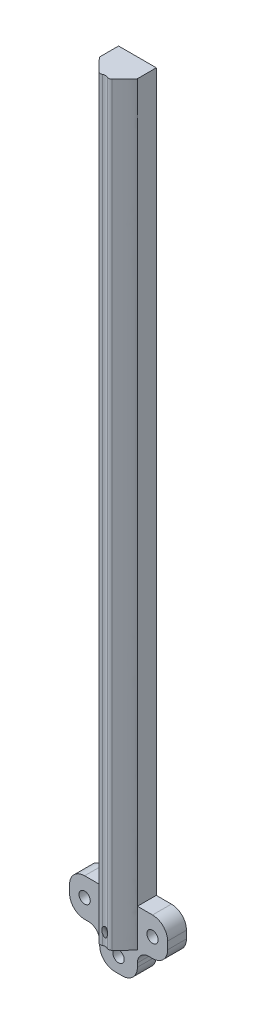
SolidWorks part; units mm, degrees
ref_plane "Front Plane" through (0, 0, 0) normal (0, 0, 1) x (1, 0, 0)
ref_plane "Top Plane" through (0, 0, 0) normal (0, 1, 0) x (1, 0, 0)
ref_plane "Right Plane" through (0, 0, 0) normal (1, 0, 0) x (0, 0, -1)
sketch "Sketch1" plane through (0, 0, 0) normal (0, 1, 0) x (1, 0, 0)
  line L1 (0, 0) -> (10, 0)
  line L2 (0, 0) -> (0, -10)
  line L3 (0, -10) -> (10, -10)
  line L4 (10, 0) -> (10, -10)
  dimension "D1" = 10
  dimension "D2" = 10
extrude "Boss-Extrude1" add sketch "Sketch1" along normal blind 200
fillet "Fillet1" radius 5 2 edges at (0, 100, 10) (10, 100, 10) conic rho 0.05
sketch "Sketch2" plane through (0, 0, 0) normal (0, -1, 0) x (-1, 0, 0)
  circle A0 centre (-5, -10) radius 1.5
  dimension "D1" = 3
extrude "Cut-Extrude1" cut sketch "Sketch2" against normal through all
fillet "Fillet2" radius 1 2 edges
sketch "Sketch4" plane through (0, 0, 0) normal (0, 0, -1) x (-1, 0, 0)
  line L1 (0, 0) -> (8, 0)
  line L2 (0, 0) -> (0, 10)
  line L3 (0, 10) -> (8, 10)
  line L4 (8, 0) -> (8, 10)
  line L5 (-10, 0) -> (-18, 0)
  line L6 (-10, 0) -> (-10, 10)
  line L7 (-10, 10) -> (-18, 10)
  line L8 (-18, 0) -> (-18, 10)
  dimension "D1" = 8
  dimension "D2" = 8
  dimension "D3" = 10
  dimension "D4" = 10
extrude "Boss-Extrude2" add sketch "Sketch4" against normal blind 5
sketch "Sketch5" plane through (0, 0, 0) normal (0, -1, 0) x (-1, 0, 0)
  line L0 (-18, 0) -> (8, 0) construction
  line L1 (0, 0) -> (-10, 0)
  line L2 (0, 0) -> (0, -5)
  line L3 (0, -5) -> (-10, -5)
  line L4 (-10, 0) -> (-10, -5)
  dimension "D1" = 5
  dimension "D2" = 0
  dimension "D3" = 0
extrude "Boss-Extrude3" add sketch "Sketch5" along normal blind 8
fillet "Fillet3" radius 4 6 edges at (18, 10, 2.5) (18, 0, 2.5) (10, -8, 2.5) (0, -8, 2.5) (-8, 10, 2.5) (-8, 0, 2.5)
fillet "Fillet4" radius 3 2 edges
sketch "Sketch6" plane through (0, 0, 5) normal (0, 0, 1) x (1, 0, 0)
  line L0 (-4, 10) -> (0, 10) construction
  line L1 (-8, 4) -> (-8, 6) construction
  line L2 (10, 10) -> (14, 10) construction
  line L3 (18, 6) -> (18, 4) construction
  line L4 (6, -8) -> (4, -8) construction
  line L5 (0, -4) -> (0, -3) construction
  circle A0 centre (-4, 5) radius 1.5
  circle A1 centre (14, 5) radius 1.5
  circle A2 centre (5, -4) radius 1.5
  dimension "D1" = 3
  dimension "D8" = 3
  dimension "D9" = 3
  dimension "D2" = 5
  dimension "D3" = 4
  dimension "D4" = 5
  dimension "D5" = 4
  dimension "D6" = 4
  dimension "D7" = 5
extrude "Cut-Extrude3" cut sketch "Sketch6" against normal through all
ref_axis "Axis1" through (10, 0, 5) along (-1, 0, 0)
ref_plane "Plane1" through (0, 2.3492, 1.6449) normal (0, 0.8192, 0.5736) x (-1, 0, 0)
sketch "Sketch7" plane through (0, 2.3492, 1.6449) normal (0, 0.8192, 0.5736) x (-1, 0, 0)
  line L0 (-10, 4.0958) -> (0, 4.0958) construction
  circle A0 centre (-5, 5.0958) radius 0.75
  dimension "D1" = 1.5
  dimension "D2" = 1
  dimension "D3" = 5
extrude "Cut-Extrude4" cut sketch "Sketch7" along normal blind 8
equation "\"滑动-垂直孔\"= 0.6"
equation "\"滑动-水平孔\"= 0.3"
equation "\"松动-垂直孔\"= 0.3"
equation "\"松动-水平孔\"= 0.1"
equation "\"正常-垂直孔\"= 0.15"
equation "\"正常-水平孔\"= 0"
equation "\"紧缩-垂直孔\"= 0"
equation "\"紧缩-水平孔\"= - 0.1"
equation "\"D1@Sketch6\"=\"紧缩-垂直孔\"+3"
equation "\"D4@Sketch6\"=\"D2@Sketch6\""
equation "\"D5@Sketch6\"=\"D3@Sketch6\""
equation "\"D6@Sketch6\"=\"D3@Sketch6\""
equation "\"D7@Sketch6\"=\"D2@Sketch6\""
equation "\"D8@Sketch6\"=\"D1@Sketch6\""
equation "\"D9@Sketch6\"=\"D1@Sketch6\""
